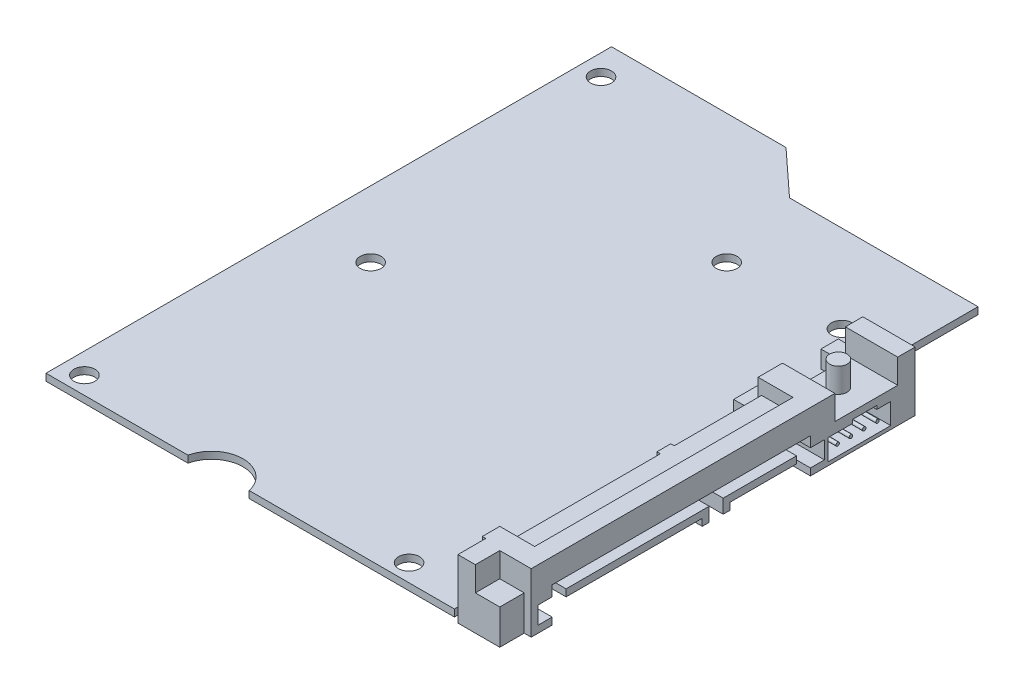
SolidWorks part; units mm, degrees
ref_plane "前视基准面" through (0, 0, 0) normal (0, 0, 1) x (1, 0, 0)
ref_plane "上视基准面" through (0, 0, 0) normal (0, 1, 0) x (1, 0, 0)
ref_plane "右视基准面" through (0, 0, 0) normal (1, 0, 0) x (0, 0, -1)
sketch "草图1" plane through (0, 0, 0) normal (0, 1, 0) x (1, 0, 0)
  line L0 (25, 81) -> (31.5, 75)
  line L1 (0, 0) -> (58.5, 0)
  line L2 (0, 0) -> (0, 81)
  line L3 (0, 81) -> (25, 81)
  line L4 (58.5, 0) -> (58.5, 75)
  line L5 (31.5, 75) -> (58.5, 75)
  dimension "D1" = 81
  dimension "D2" = 58.5
  dimension "D3" = 75
  dimension "D4" = 25
  dimension "D5" = 27
extrude "凸台-拉伸1" add sketch "草图1" along normal blind 1
sketch "草图2" plane through (0, 0, 0) normal (0, -1, 0) x (1, 0, 0)
  line L0 (59, -4) -> (55, -4)
  line L1 (55, -4) -> (55, -8)
  line L2 (55, -8) -> (59, -8)
  line L3 (59, -8) -> (59, -29)
  line L7 (59, -31) -> (59, -43.5)
  line L8 (59, -43.5) -> (55, -43.5)
  line L9 (55, -43.5) -> (55, -47)
  line L10 (55, -47) -> (59, -47)
  line L11 (59, -47) -> (59, -56)
  line L12 (59, -56) -> (55, -56)
  line L13 (55, -56) -> (55, -58.5)
  line L14 (55, -58.5) -> (66, -58.5)
  line L15 (66, -58.5) -> (66, 0)
  line L16 (66, 0) -> (59, 0)
  line L17 (59, 0) -> (59, -4)
  line L18 (58.5, 0) -> (58.5, -75) construction
  line L19 (0.55, 0) -> (-0.55, 0) construction
  line L20 (59, -29) -> (57.5, -29)
  line L21 (57.5, -29) -> (57.5, -31)
  line L22 (57.5, -31) -> (59, -31)
  line L23 (58.5, -75) -> (31.5, -75) construction
  dimension "D1" = 0.5
  dimension "D2" = 0
  dimension "D3" = 4
  dimension "D4" = 15
  dimension "D5" = 2.5
  dimension "D6" = 3.5
  dimension "D7" = 4
  dimension "D8" = 16.5
  dimension "D9" = 1.5
  dimension "D10" = 2
  dimension "D11" = 7
  dimension "D12" = 0.5
  dimension "D13" = 4
  dimension "D14" = 21
extrude "凸台-拉伸2" add sketch "草图2" along normal blind 0.5
sketch "草图3" plane through (0, -0.5, 0) normal (0, -1, 0) x (1, 0, 0)
  line L0 (66, 0) -> (59, 0)
  line L1 (59, 0) -> (59, -4)
  line L2 (59, -4) -> (55, -4)
  line L3 (55, -4) -> (55, -8)
  line L4 (55, -8) -> (59, -8)
  line L5 (59, -8) -> (59, -29)
  line L6 (59, -29) -> (57.5, -29)
  line L7 (57.5, -29) -> (57.5, -31)
  line L8 (57.5, -31) -> (59, -31)
  line L9 (59, -31) -> (59, -43.5)
  line L10 (59, -31) -> (59, -43.5) construction
  line L11 (59, -43.5) -> (55, -43.5)
  line L12 (55, -43.5) -> (55, -47)
  line L13 (55, -47) -> (59, -47)
  line L14 (59, -47) -> (59, -56)
  line L15 (59, -56) -> (55, -56)
  line L16 (55, -56) -> (55, -58.5)
  line L17 (55, -58.5) -> (66, -58.5)
  line L18 (66, -58.5) -> (66, 0)
extrude "凸台-拉伸3" add sketch "草图3" against normal blind 8.5
sketch "草图5" plane through (0, 0, -4) normal (0, 0, 1) x (1, 0, 0)
  line L0 (58.5, 0) -> (58.5, 1) construction
  line L1 (55, 8) -> (58.5, 8)
  line L2 (55, 8) -> (55, 3.5)
  line L3 (55, 3.5) -> (58.5, 3.5)
  line L4 (58.5, 8) -> (58.5, 3.5)
  line L5 (58.5, 1) -> (55, 1) construction
  dimension "D1" = 2.5
extrude "切除-拉伸1" cut sketch "草图5" against normal up to surface (54.5 mm away) up to face at (58.625, 2.125, -58.5)
sketch "草图6" plane through (0, 8, 0) normal (0, 1, 0) x (1, 0, 0)
  line L0 (66, 58.5) -> (66, 0) construction
  line L1 (66, 56) -> (59, 56)
  line L2 (66, 56) -> (66, 47)
  line L3 (66, 47) -> (59, 47)
  line L4 (59, 56) -> (59, 47)
  line L5 (59, 47) -> (59, 56) construction
  line L7 (66, 0) -> (61.5, 0)
  line L8 (66, 0) -> (66, 3.5)
  line L9 (66, 3.5) -> (61.5, 3.5)
  line L10 (61.5, 0) -> (61.5, 3.5)
  line L12 (58.5, 56) -> (55, 56) construction
  dimension "D1" = 4.5
  dimension "D2" = 3.5
extrude "切除-拉伸2" cut sketch "草图6" against normal blind 3.5
sketch "草图7" plane through (0, 4.5, 0) normal (0, 1, 0) x (1, 0, 0)
  line L0 (59, 56) -> (59, 47) construction
  line L1 (66, 56) -> (58.5, 56) construction
  circle A0 centre (62, 51.5) radius 1.25
  dimension "D1" = 2.5
  dimension "D2" = 3
  dimension "D3" = 4.5
extrude "凸台-拉伸5" add sketch "草图7" along normal blind 3.5
sketch "草图10" plane through (0, 8, 0) normal (0, 1, 0) x (1, 0, 0)
  line L0 (66, 47) -> (66, 3.5) construction
  line L1 (63.5, 6.5) -> (58.5, 6.5)
  line L2 (63.5, 6.5) -> (63.5, 43.5)
  line L3 (63.5, 43.5) -> (58.5, 43.5)
  line L4 (58.5, 6.5) -> (58.5, 43.5)
  line L5 (66, 3.5) -> (61.5, 3.5) construction
  dimension "D1" = 2.5
  dimension "D2" = 3
extrude "切除-拉伸3" cut sketch "草图10" against normal blind 2
sketch "草图11" plane through (0, -0.5, 0) normal (0, -1, 0) x (1, 0, 0)
  line L0 (66, -58.5) -> (66, 0) construction
  line L1 (61, -6.5) -> (66, -6.5)
  line L2 (61, -6.5) -> (61, -43.5)
  line L3 (61, -43.5) -> (66, -43.5)
  line L4 (66, -6.5) -> (66, -43.5)
  line L5 (59, -8) -> (59, -29) construction
  line L6 (66, 0) -> (59, 0) construction
  dimension "D1" = 37
  dimension "D2" = 2
  dimension "D3" = 6.5
extrude "切除-拉伸4" cut sketch "草图11" against normal blind 5
sketch "草图12" plane through (66, 0, 0) normal (1, 0, 0) x (0, 0, -1)
  line L0 (6.5, -0.5) -> (0, -0.5) construction
  line L1 (0, 4.5) -> (3.5, 4.5)
  line L2 (0, 4.5) -> (0, -0.5)
  line L3 (0, -0.5) -> (3.5, -0.5)
  line L4 (3.5, 4.5) -> (3.5, -0.5)
  line L5 (3.5, 4.5) -> (3.5, 8) construction
extrude "切除-拉伸5" cut sketch "草图12" against normal blind 1
sketch "草图13" plane through (66, 0, 0) normal (1, 0, 0) x (0, 0, -1)
  line L1 (4.5, 3) -> (7.5, 3)
  line L2 (4.5, 3) -> (4.5, 0.5)
  line L3 (4.5, 0.5) -> (7.5, 0.5)
  line L6 (42.5, 3) -> (45.5, 3)
  line L8 (42.5, 0.5) -> (45.5, 0.5)
  line L9 (45.5, 3) -> (45.5, 0.5)
  line L10 (6.5, 4.5) -> (6.5, -0.5) construction
  line L11 (6.5, -0.5) -> (3.5, -0.5) construction
  line L12 (7.5, 3) -> (7.5, 0.5)
  line L13 (42.5, 3) -> (42.5, 0.5)
  dimension "D1" = 41
  dimension "D2" = 2
  dimension "D3" = 2.5
  dimension "D4" = 1
  dimension "D5" = 3
extrude "切除-拉伸6" cut sketch "草图13" against normal blind 8
sketch "草图14" plane through (66, 0, 0) normal (1, 0, 0) x (0, 0, -1)
  line L0 (36.3, 0) -> (-36.3, 0) construction
  line L1 (46, 3) -> (49.5, 3)
  line L2 (46, 3) -> (46, 0)
  line L3 (46, 0) -> (55, 0)
  line L4 (55, 3) -> (55, 0)
  line L5 (45.5, 0.5) -> (45.5, 3) construction
  line L7 (49.5, 3) -> (49.5, 3.5)
  line L8 (49.5, 3.5) -> (53, 3.5)
  line L9 (53, 3) -> (53, 3.5)
  line L10 (46, 1.5) -> (55, 1.5) construction
  line L11 (53, 3) -> (55, 3)
  dimension "D1" = 9
  dimension "D2" = 3
  dimension "D3" = 0.5
  dimension "D4" = 3.5
  dimension "D5" = 0.5
  dimension "D6" = 2
extrude "切除-拉伸7" cut sketch "草图14" against normal blind 5
sketch "草图15" plane through (61, 0, 0) normal (1, 0, 0) x (0, 0, -1)
  line L0 (46, 1.5) -> (55, 1.5) construction
  line L1 (46, 3) -> (46, 0) construction
  line L2 (55, 0) -> (55, 3) construction
  line L3 (46, 3) -> (46, 0) construction
  circle A0 centre (47.4, 1.5) radius 0.25
  dimension "D2" = 0.5
  dimension "D1" = 1.4
extrude "凸台-拉伸6" add sketch "草图15" along normal up to surface (5 mm away) up to face at (66, 2.375, -50.875)
pattern_linear "阵列(线性)1" count 4 spacing 1.9 along (0, 0, -1) of "凸台-拉伸6"
sketch "草图16" plane through (61, 0, 0) normal (1, 0, 0) x (0, 0, -1)
  line L0 (8.5, 2) -> (8.5, 3)
  line L1 (8.5, 3) -> (29, 3)
  line L2 (29, 3) -> (29, 1)
  line L3 (29, 1) -> (28, 1)
  line L4 (28, 1) -> (28, 2)
  line L5 (28, 2) -> (8.5, 2)
  line L6 (6.5, 0.5) -> (6.5, -0.5) construction
  line L7 (36.3, 0) -> (-36.3, 0) construction
  line L8 (31, 1) -> (31, 3)
  line L9 (31, 3) -> (41.5, 3)
  line L10 (41.5, 3) -> (41.5, 2)
  line L11 (41.5, 2) -> (32, 2)
  line L12 (32, 2) -> (32, 1)
  line L13 (32, 1) -> (31, 1)
  dimension "D1" = 1
  dimension "D2" = 19.5
  dimension "D3" = 1
  dimension "D4" = 2
  dimension "D5" = 1
  dimension "D6" = 9.5
  dimension "D7" = 2
extrude "凸台-拉伸7" add sketch "草图16" along normal up to surface (5 mm away) up to face at (66, 2.375, -50.875)
sketch "草图17" plane through (0, 1, 0) normal (0, 1, 0) x (1, 0, 0)
  line L0 (3, 2.5) -> (51.8297, 2.5) construction
  line L5 (0, -4.675) -> (0, 4.675) construction
  line L6 (3, 76.5) -> (3, -2.3373) construction
  line L7 (35, 62.5) -> (56.6467, 62.5) construction
  line L8 (-4.675, 0) -> (4.675, 0) construction
  line L13 (66, 47) -> (66, 3.5) construction
  line L15 (66, 58.5) -> (66, 56) construction
  circle A0 centre (3, 76.5) radius 1.5
  circle A1 centre (35, 62.5) radius 1.5
  circle A2 centre (51.5, 62.5) radius 1.5
  circle A3 centre (3, 2.5) radius 1.5
  circle A4 centre (9.5, 37) radius 1.5
  circle A5 centre (49.5, 2.5) radius 1.5
  dimension "D2" = 46.5
  dimension "D3" = 3
  dimension "D1" = 74
  dimension "D4" = 2.5
  dimension "D5" = 3
  dimension "D6" = 56.5
  dimension "D7" = 37
  dimension "D8" = 14.5
  dimension "D9" = 60
  dimension "D10" = 16.5
extrude "切除-拉伸8" cut sketch "草图17" against normal blind 5
sketch "草图18" plane through (0, 1, 0) normal (0, 1, 0) x (1, 0, 0)
  line L0 (25, 81) -> (0, 81) construction
  line L1 (66, 6.5) -> (66, 3.5) construction
  circle A0 centre (24.72, -1) radius 4.5
  dimension "D1" = 9
  dimension "D2" = 82
  dimension "D3" = 41.28
extrude "切除-拉伸9" cut sketch "草图18" against normal through all
sketch "草图19" plane through (0, 2, 0) normal (0, -1, 0) x (1, 0, 0)
  line L0 (61, -6.5) -> (61, -43.5) construction
  line L1 (61, -8.6) -> (65.5, -8.6)
  line L2 (61, -8.6) -> (61, -9.6)
  line L3 (61, -9.6) -> (65.5, -9.6)
  line L4 (65.5, -8.6) -> (65.5, -9.6)
  line L5 (66, -8.5) -> (61, -8.5) construction
  dimension "D1" = 4.5
  dimension "D2" = 1
  dimension "D3" = 0.1
extrude "凸台-拉伸8" add sketch "草图19" along normal blind 0.1
chamfer "倒角1" distance 0.1 angle 45 1 edges at (65.5, 1.9, -9.1)
pattern_linear "阵列(线性)3" count 15 spacing 1.3 along (0, 0, -1) of "凸台-拉伸8", "倒角1"
sketch "草图20" plane through (0, 2, 0) normal (0, -1, 0) x (1, 0, 0)
  line L0 (61, -6.5) -> (61, -43.5) construction
  line L1 (61, -41.1) -> (65.5, -41.1)
  line L2 (61, -41.1) -> (61, -40.1)
  line L3 (61, -40.1) -> (65.5, -40.1)
  line L4 (65.5, -41.1) -> (65.5, -40.1)
  line L5 (66, -41.5) -> (61, -41.5) construction
  dimension "D1" = 4.5
  dimension "D2" = 1
  dimension "D3" = 0.4
extrude "凸台-拉伸9" add sketch "草图20" along normal blind 0.1
chamfer "倒角2" distance 0.1 angle 45 1 edges at (65.5, 1.9, -40.6)
pattern_linear "阵列(线性)4" count 7 spacing 1.3 along (0, 0, 1) of "凸台-拉伸9", "倒角2"
